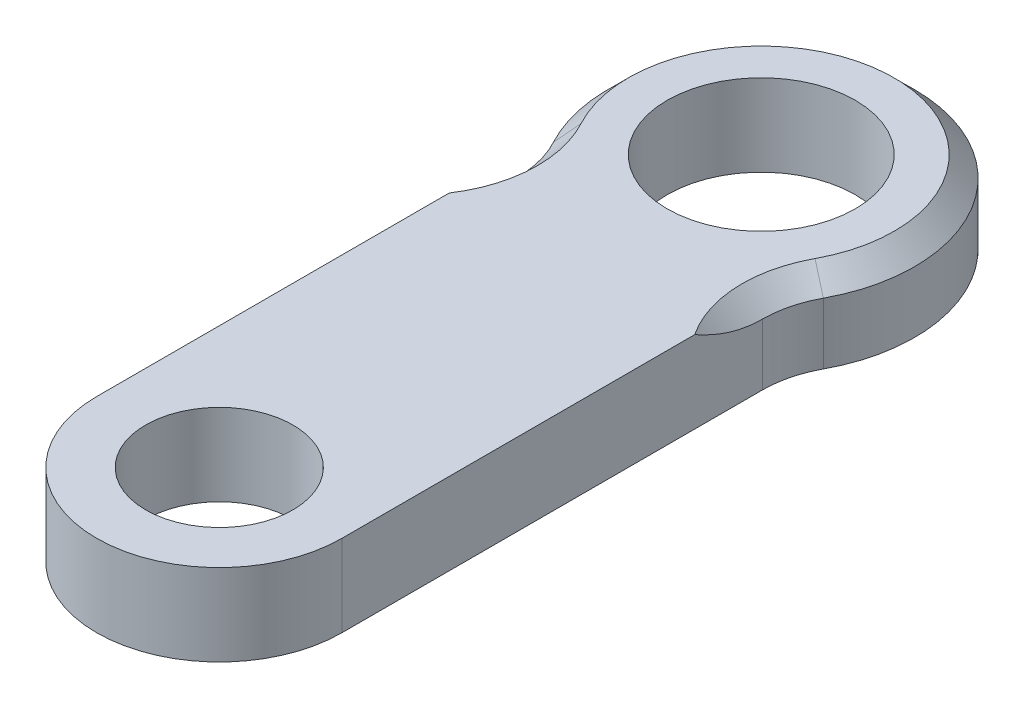
SolidWorks part; units mm, degrees
material "3D printed plastic"
ref_plane "Front Plane" through (0, 0, 0) normal (0, 0, 1) x (1, 0, 0)
ref_plane "Top Plane" through (0, 0, 0) normal (0, 1, 0) x (1, 0, 0)
ref_plane "Right Plane" through (0, 0, 0) normal (1, 0, 0) x (0, 0, -1)
sketch "Sketch1" plane through (0, 0, 0) normal (0, 1, 0) x (1, 0, 0)
  line L0 (0, 0) -> (0, -26.5) construction
  line L1 (6, 0) -> (6, -26.5)
  line L2 (-6, 0) -> (-6, -26.5)
  circle A0 centre (0, 0) radius 4.6
  circle A1 centre (0, -26.5) radius 3.6
  arc A2 (6, 0) -> (-6, 0) centre (0, 0) ccw
  arc A3 (-6, -26.5) -> (6, -26.5) centre (0, -26.5) ccw
  point P5 (0, -13.25)
  dimension "D1" = 0
  dimension "D2" = 26.5
  dimension "D3" = 9.2
  dimension "D5" = 7.2
  dimension "D4" = 12
extrude "Boss-Extrude1" add sketch "Sketch1" along normal blind 4
sketch "Sketch2" plane through (0, 4, 0) normal (0, 1, 0) x (1, 0, 0)
  circle A0 centre (0, 0) radius 4.6
  circle A1 centre (0, 0) radius 7.5
  circle A2 centre (0, 0) radius 4.6 construction
  dimension "D1" = 15
extrude "Boss-Extrude2" add sketch "Sketch2" against normal up to surface (4 mm away) up to face at (0, 0, 4.6)
fillet "Fillet1" radius 5 2 edges at (6, 2, 4.5) (-6, 2, 4.5)
chamfer "Chamfer2" distance 1 angle 45 1 edges at (0, 4, -7.5)
